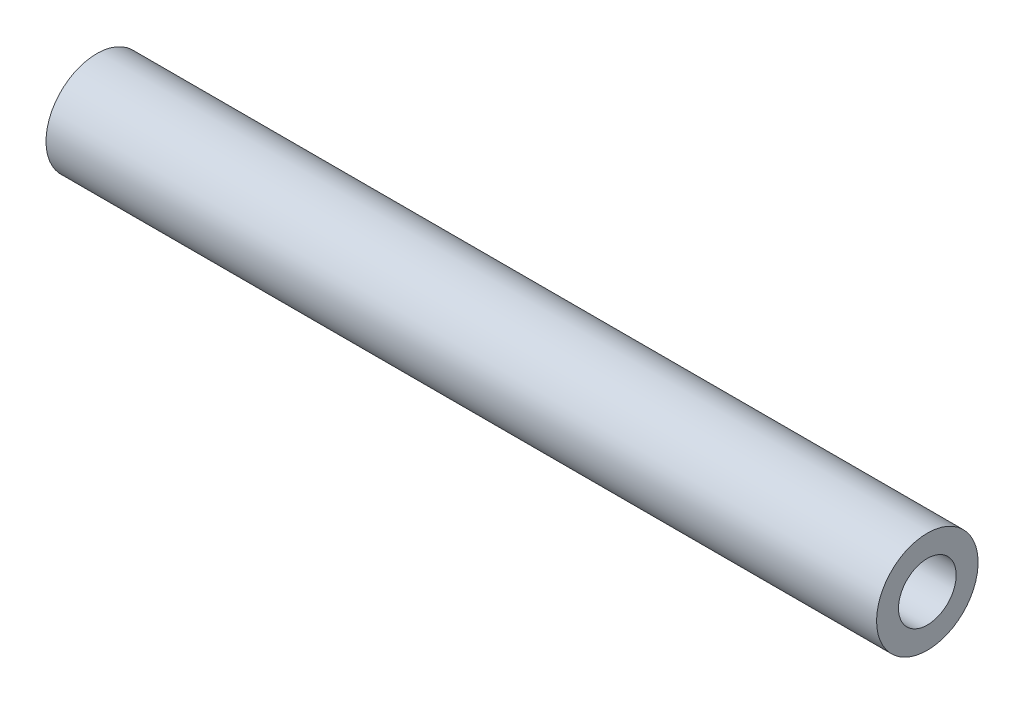
SolidWorks part; units mm, degrees
ref_plane "Front Plane" through (0, 0, 0) normal (0, 0, 1) x (1, 0, 0)
ref_plane "Top Plane" through (0, 0, 0) normal (0, 1, 0) x (1, 0, 0)
ref_plane "Right Plane" through (0, 0, 0) normal (1, 0, 0) x (0, 0, -1)
sketch "Sketch1" plane through (0, 0, 0) normal (1, 0, 0) x (0, 0, -1)
  circle A0 centre (0, 0) radius 22
  circle A1 centre (0, 0) radius 12.5
  dimension "D1" = 44
  dimension "D2" = 25
extrude "Boss-Extrude1" add sketch "Sketch1" along normal blind 360
